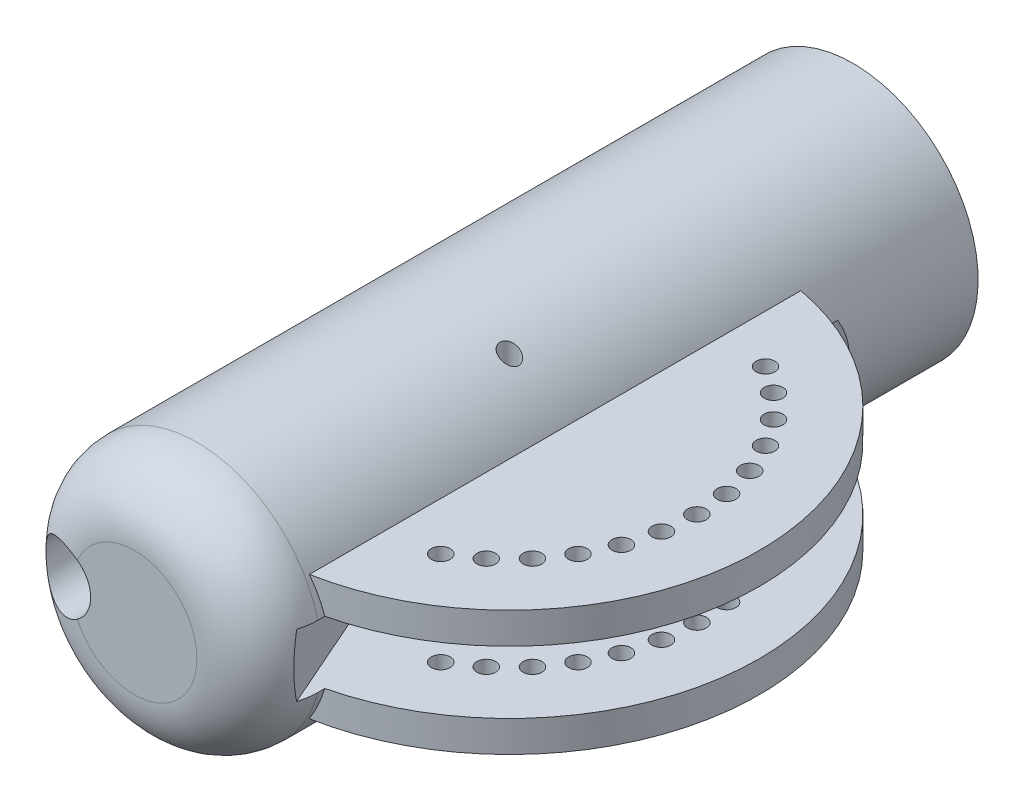
SolidWorks part; units mm, degrees
ref_plane "Alzado" through (0, 0, 0) normal (0, 0, 1) x (1, 0, 0)
ref_plane "Planta" through (0, 0, 0) normal (0, 1, 0) x (1, 0, 0)
ref_plane "Vista lateral" through (0, 0, 0) normal (1, 0, 0) x (0, 0, -1)
sketch "Croquis4" plane through (0, 0, 0) normal (0, 0, 1) x (1, 0, 0)
  circle A0 centre (0, 0) radius 20
  dimension "D1" = 40
extrude "Saliente-Extruir2" add sketch "Croquis4" against normal blind 100
fillet "Redondeo1" radius 10 1 edges at (20, 0, 0)
sketch "Croquis8" plane through (0, 0, 0) normal (0, 1, 0) x (1, 0, 0)
  line L0 (10, 48.5) -> (10, 10)
  line L3 (10, 90) -> (10, 51.5)
  arc A0 (10, 48.5) -> (10, 51.5) centre (10, 50) ccw
  arc A1 (10, 10) -> (10, 90) centre (10, 50) ccw
  dimension "D3" = 80
  dimension "D4" = 3
extrude "Saliente-Extruir6" add sketch "Croquis8" along normal blind 10
sketch "Croquis6" plane through (0, 0, -100) normal (0, 0, -1) x (-1, 0, 0)
  circle A0 centre (0, 0) radius 4
  circle A1 centre (0, 0) radius 6
  circle A2 centre (0, 0) radius 20
  circle A3 centre (0, 0) radius 17
  circle M1 centre (0, 0) radius 20
  dimension "D1" = 12
  dimension "D2" = 8
  dimension "D3" = 34
extrude "Saliente-Extruir4" add sketch "Croquis6" along normal blind 15 contours A1 A0 region at (5.8303, 0, -100)
mirror "Simetría1" about plane through (0, 0, 0) normal (0, 1, 0) of "Saliente-Extruir6"
sketch "Croquis15" plane through (0, 0, 0) normal (0, 0, 1) x (1, 0, 0)
  line L0 (38.5, 0) -> (-38.5, 0) construction
  line L2 (0, -22) -> (0, 22) construction
  circle A0 centre (-12, 0) radius 5
  point P2 (-8.18, 0)
  point P8 (-10, 0)
  point P9 (-10, 0)
  dimension "D2" = 10
  dimension "1" = 12
extrude "Cortar-Extruir5" cut sketch "Croquis15" against normal blind 91 contours A0
sketch "Croquis10" plane through (0, 0, 0) normal (0, 1, 0) x (1, 0, 0)
  line L0 (50, 50) -> (10, 50) construction
  line L1 (17.3205, 89.3244) -> (17.3205, 10.6756)
  arc A0 (17.3205, 10.6756) -> (17.3205, 89.3244) centre (10, 50) ccw construction
  arc A1 (17.3205, 10.6756) -> (17.3205, 89.3244) centre (10, 50) ccw
extrude "Cortar-Extruir2" cut sketch "Croquis10" against normal blind 5
mirror "Simetría2" about plane through (0, 0, 0) normal (0, 1, 0) of "Cortar-Extruir2"
sketch "Croquis11" plane through (0, 0, 0) normal (0, 1, 0) x (1, 0, 0)
  line L0 (50, 50) -> (40, 50) construction
  line L1 (40, 50) -> (40, 84.6) construction
  line L2 (40, 84.6) -> (31.8206, 78.5564) construction
  line L3 (40, 50) -> (40, 15.4) construction
  line L4 (17.3205, 89.3244) -> (2.0687, 54.9626)
  line L11 (17.3205, 10.6756) -> (2.052, 45.4012)
  line L13 (17.3205, 89.3244) -> (20, 94.3649)
  line L14 (20, 88.7298) -> (20, 100) construction
  line L15 (20, 10) -> (20, -18.8157) construction
  line L16 (13.1254, 20.2167) -> (25.5879, -8.1273) construction
  line L17 (17.3205, 10.6756) -> (20, 4.5815)
  line L18 (20, 4.5815) -> (20, 94.3649)
  arc A0 (17.3205, 10.6756) -> (17.3205, 89.3244) centre (10, 50) ccw construction
  arc A3 (2.052, 45.4012) -> (2.0687, 54.9626) centre (12.882, 50.163) cw
  dimension "D3" = 34.6
  dimension "D4" = 34.6
extrude "Cortar-Extruir3" cut sketch "Croquis11" against normal blind 5
mirror "Simetría3" about plane through (0, 0, 0) normal (0, 1, 0) of "Cortar-Extruir3"
sketch "Croquis12" plane through (0, 0, 0) normal (0, 1, 0) x (1, 0, 0)
  line L0 (50, 50) -> (10, 50) construction
  line L1 (10, 50) -> (39.5442, 55.2094) construction
  line L2 (10, 50) -> (38.1908, 60.2606) construction
  line L3 (10, 50) -> (35.9808, 65) construction
  line L4 (10, 50) -> (32.9813, 69.2836) construction
  line L5 (10, 50) -> (29.2836, 72.9813) construction
  line L6 (10, 50) -> (25, 75.9808) construction
  line L7 (10, 50) -> (39.5442, 44.7906) construction
  line L8 (10, 50) -> (38.1908, 39.7394) construction
  line L9 (10, 50) -> (35.9808, 35) construction
  line L10 (10, 50) -> (32.9813, 30.7164) construction
  line L11 (10, 50) -> (29.2836, 27.0187) construction
  line L12 (10, 50) -> (25, 24.0192) construction
  arc A0 (17.3205, 10.6756) -> (17.3205, 89.3244) centre (10, 50) ccw construction
  circle A1 centre (10, 50) radius 1.5
  circle A3 centre (40, 50) radius 1.5
  circle A4 centre (39.5442, 55.2094) radius 1.5
  circle A5 centre (38.1908, 60.2606) radius 1.5
  circle A6 centre (35.9808, 65) radius 1.5
  circle A7 centre (32.9813, 69.2836) radius 1.5
  circle A8 centre (29.2836, 72.9813) radius 1.5
  circle A9 centre (25, 75.9808) radius 1.5
  circle A10 centre (39.5442, 44.7906) radius 1.5
  circle A11 centre (38.1908, 39.7394) radius 1.5
  circle A12 centre (35.9808, 35) radius 1.5
  circle A13 centre (32.9813, 30.7164) radius 1.5
  circle A14 centre (29.2836, 27.0187) radius 1.5
  circle A15 centre (25, 24.0192) radius 1.5
  dimension "D2" = 3
  dimension "D3" = 3
  dimension "D10" = 3
  dimension "D11" = 3
  dimension "D12" = 3
  dimension "D13" = 3
  dimension "D14" = 3
  dimension "D15" = 3
  dimension "D16" = 3
  dimension "D17" = 3
  dimension "D18" = 3
  dimension "D19" = 3
  dimension "D20" = 3
  dimension "D21" = 3
  dimension "D4" = 10
  dimension "D5" = 10
  dimension "D6" = 10
  dimension "D7" = 10
  dimension "D8" = 10
  dimension "D9" = 10
extrude "Cortar-Extruir4" cut sketch "Croquis12" against normal blind 48
extrude "Cortar-Extruir1" cut sketch "Croquis6<7>" against normal blind 10 contours A1 region at (16.5192, 0, -100)
sketch "Croquis6<7>" plane through (0, 0, -100) normal (0, 0, -1) x (-1, 0, 0) same geometry as "Croquis6"
mirror "Simetría4" about plane through (0, 0, 0) normal (0, 1, 0) of "Cortar-Extruir4"
extrude "Saliente-Extruir11" add sketch "Croquis6<8>" along normal blind 15 contours A3 M1 region at (19.4343, 0, -100)
sketch "Croquis6<8>" plane through (0, 0, -100) normal (0, 0, -1) x (-1, 0, 0) same geometry as "Croquis6"
